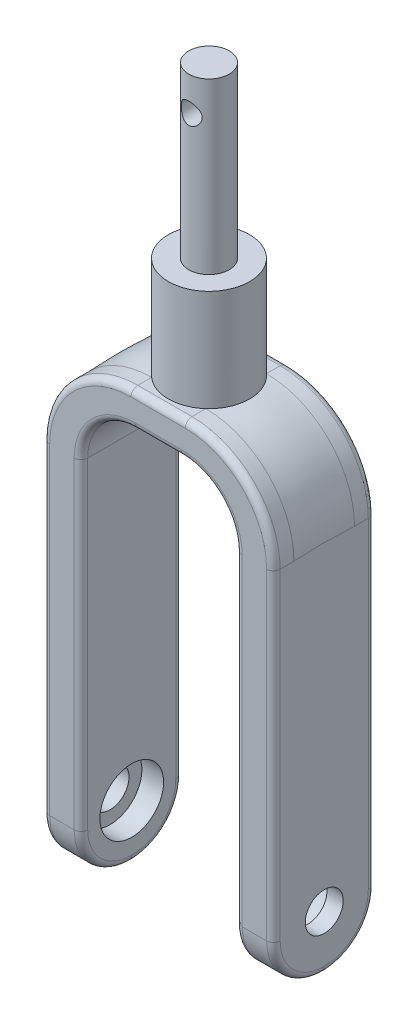
SolidWorks part; units mm, degrees
ref_plane "前视基准面" through (0, 0, 0) normal (0, 0, 1) x (1, 0, 0)
ref_plane "上视基准面" through (0, 0, 0) normal (0, 1, 0) x (1, 0, 0)
ref_plane "右视基准面" through (0, 0, 0) normal (1, 0, 0) x (0, 0, -1)
sketch "草图1" plane through (0, 0, 0) normal (0, 1, 0) x (1, 0, 0)
  line L1 (17, 7.5) -> (-17, 7.5)
  line L2 (17, 7.5) -> (17, -7.5)
  line L3 (17, -7.5) -> (-17, -7.5)
  line L4 (-17, 7.5) -> (-17, -7.5)
  line L5 (17, 7.5) -> (-17, -7.5) construction
  line L6 (17, -7.5) -> (-17, 7.5) construction
  point P0 (0, 0)
extrude "凸台-拉伸1" add sketch "草图1" against normal blind 68
sketch "草图2" plane through (0, 0, 0) normal (0, 1, 0) x (1, 0, 0)
  circle A0 centre (0, 0) radius 6
extrude "凸台-拉伸2" add sketch "草图2" along normal blind 15
sketch "草图7" plane through (0, 15, 0) normal (0, 1, 0) x (1, 0, 0)
  circle A0 centre (0, 0) radius 2.98
extrude "凸台-拉伸3" add sketch "草图7" along normal blind 25
sketch "草图8" plane through (0, 0, 0) normal (0, 0, 1) x (1, 0, 0)
  line L0 (0, 15) -> (0, 35) construction
  line L1 (6, 15) -> (-6, 15) construction
  circle A1 centre (0, 35) radius 1.55
extrude "切除-拉伸5" cut sketch "草图8" against normal through all both and the other way through all
sketch "草图3" plane through (0, 0, 7.5) normal (0, 0, 1) x (1, 0, 0)
  line L0 (-17, -68) -> (17, -68) construction
  line L1 (-11.4, -68) -> (11.4, -68)
  line L2 (-11.4, -68) -> (-11.4, -5)
  line L3 (-11.4, -5) -> (11.4, -5)
  line L4 (11.4, -68) -> (11.4, -5)
extrude "切除-拉伸1" cut sketch "草图3" against normal through all
fillet "圆角1" radius 8 2 edges at (11.4, -5, 0) (-11.4, -5, 0)
fillet "圆角5" radius 13 2 edges at (17, 0, 0) (-17, 0, 0)
fillet "圆角3" radius 7.5 4 edges at (14.2, -68, -7.5) (14.2, -68, 7.5) (-14.2, -68, -7.5) (-14.2, -68, 7.5)
fillet "圆角2" radius 1 28 edges at (-17, -36.75, -7.5) (0, 0, -7.5) (17, -36.75, -7.5) (17, -36.75, 7.5) (0, 0, 7.5) (-17, -36.75, 7.5) (-9.0569, -7.3431, 7.5) (0, -5, 7.5) (9.0569, -7.3431, 7.5) (11.4, -36.75, 7.5) (11.4, -36.75, -7.5) (9.0569, -7.3431, -7.5) (0, -5, -7.5) (-9.0569, -7.3431, -7.5) (-11.4, -36.75, -7.5) (-11.4, -36.75, 7.5) (11.4, -65.8033, 5.3033) (11.4, -65.8033, -5.3033) (-11.4, -65.8033, -5.3033) (-11.4, -65.8033, 5.3033) (-17, -65.8033, 5.3033) (-17, -65.8033, -5.3033) (17, -65.8033, -5.3033) (17, -65.8033, 5.3033) (-13.1924, -3.8076, -7.5) (13.1924, -3.8076, -7.5) (13.1924, -3.8076, 7.5) (-13.1924, -3.8076, 7.5)
sketch "草图4" plane through (17, 0, 0) normal (1, 0, 0) x (0, 0, -1)
  circle A0 centre (0, -60) radius 2.8
extrude "切除-拉伸2" cut sketch "草图4" against normal through all
sketch "草图6" plane through (11.4, 0, 0) normal (1, 0, 0) x (0, 0, -1)
  circle A0 centre (0, -60) radius 4.7
extrude "切除-拉伸4" cut sketch "草图6" along normal blind 3.2
mirror "镜向1" about plane through (0, 0, 0) normal (1, 0, 0) of "切除-拉伸4"
